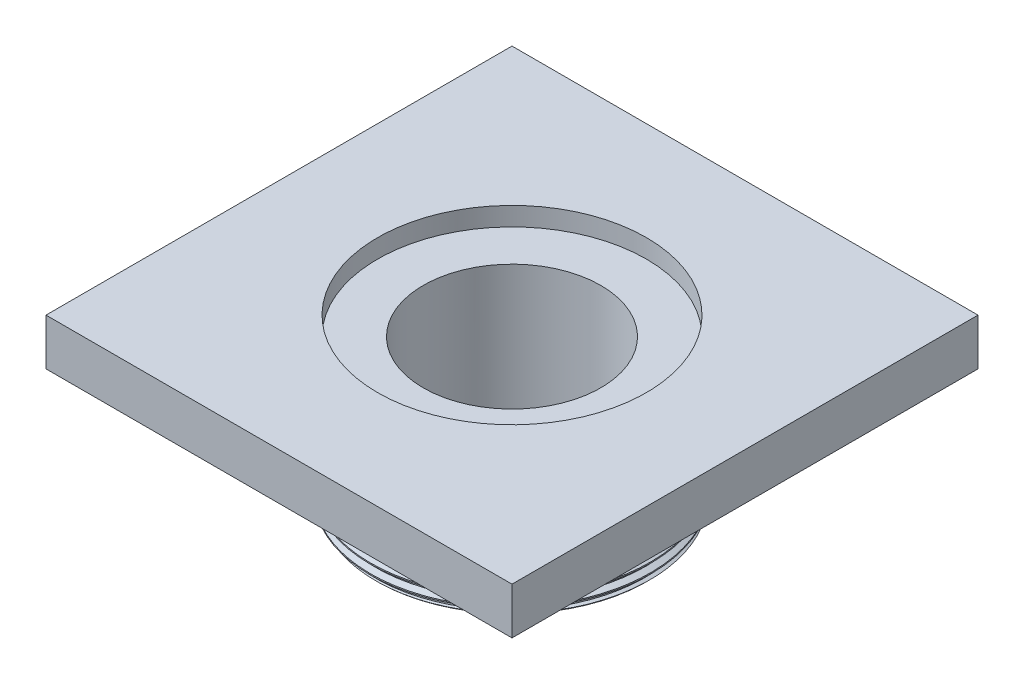
SolidWorks part; units mm, degrees
material "ABS"
ref_plane "Alzado" through (0, 0, 0) normal (0, 0, 1) x (1, 0, 0)
ref_plane "Planta" through (0, 0, 0) normal (0, 1, 0) x (1, 0, 0)
ref_plane "Vista lateral" through (0, 0, 0) normal (1, 0, 0) x (0, 0, -1)
sketch "Sketch1" plane through (0, 0, 0) normal (0, 1, 0) x (1, 0, 0)
  line L1 (-25, -25) -> (25, -25)
  line L2 (-25, -25) -> (-25, 25)
  line L3 (-25, 25) -> (25, 25)
  line L4 (25, -25) -> (25, 25)
  line L5 (-25, -25) -> (25, 25) construction
  line L6 (-25, 25) -> (25, -25) construction
  point P0 (0, 0)
  dimension "D1" = 50
  dimension "D2" = 50
extrude "Boss-Extrude1" add sketch "Sketch1" along normal blind 5
sketch "Sketch2" plane through (0, 0, 0) normal (0, -1, 0) x (1, 0, 0)
  circle A0 centre (0, 0) radius 15
  dimension "D1" = 30
extrude "Boss-Extrude2" add sketch "Sketch2" along normal blind 12.5
fillet "Fillet1" radius 2 1 edges at (0, 0, -15)
sketch "Sketch3" plane through (0, -12.5, 0) normal (0, -1, 0) x (1, 0, 0)
  circle A0 centre (0, 0) radius 9.525
extrude "Cut-Extrude1" cut sketch "Sketch3" against normal through all
chamfer "Chamfer1" distance 0.5 angle 45 1 edges at (0, -12.5, -15)
thread "Thread1" pitch 1 method cut profile "Perfil de rosca1" start angle 0, offset 0, length 10.922, pitch 1, diameter 30
ref_plane "Plane1" through (-15, -2, 0) normal (0, 0, 1) x (-1, 0, 0)
sketch "Perfil de rosca1" plane through (-15, -2, 0) normal (0, 0, 1) x (-1, 0, 0)
  line L0 (0, 0) -> (0, 1) construction
  line L11 (0, 0) -> (0, 0.875)
  line L12 (0, 0.875) -> (-0.5413, 0.5625)
  line L13 (-0.5413, 0.5625) -> (-0.5413, 0.3125)
  line L15 (-0.5413, 0.3125) -> (0, 0)
  line L17 (-0.5413, 0.4375) -> (0, 0.4375) construction
  point P2 (0, 0)
  dimension "Pitch" = 1
  dimension "Profile_Angle" = 60
  dimension "Profile_Land" = 0.25
  dimension "Profile_Height" = 0.5413
sketch "Sketch6" plane through (0, 5, 0) normal (0, 1, 0) x (1, 0, 0)
  circle A0 centre (0, 0) radius 14.4159
extrude "Cut-Extrude2" cut sketch "Sketch6" against normal blind 2
